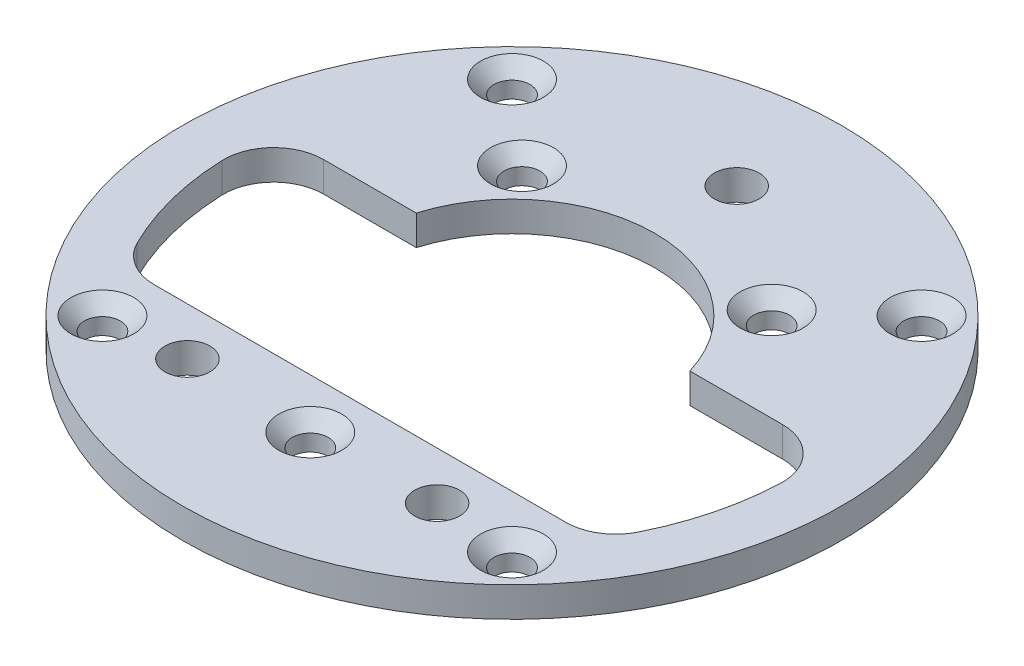
SolidWorks part; units mm, degrees
material "ABS"
ref_plane "Front Plane" through (0, 0, 0) normal (0, 0, 1) x (1, 0, 0)
ref_plane "Top Plane" through (0, 0, 0) normal (0, 1, 0) x (1, 0, 0)
ref_plane "Right Plane" through (0, 0, 0) normal (1, 0, 0) x (0, 0, -1)
sketch "Sketch1" plane through (0, 0, 0) normal (0, 1, 0) x (1, 0, 0)
  circle A0 centre (0, 0) radius 33
  circle A1 centre (0, 0) radius 28
  dimension "D1" = 66
  dimension "D2" = 5
extrude "Boss-Extrude1" add sketch "Sketch1" along normal blind 3
sketch "Sketch2" plane through (0, 3, 0) normal (0, 1, 0) x (1, 0, 0)
  line L0 (-23.5, -15.2233) -> (23.5, -15.2233)
  line L1 (-27.6968, 4.1095) -> (-13.6968, 4.1095)
  line L2 (0, 0) -> (7.7557, 0) construction
  line L3 (13.6968, 4.1095) -> (27.6968, 4.1095)
  line L4 (-20.5061, 20.5061) -> (0, 0) construction
  line L5 (-12.5, 13.5) -> (12.5, 13.5) construction
  circle A0 centre (0, 22.5) radius 2.25 construction
  circle A1 centre (-12.5, -20) radius 2.25 construction
  circle A2 centre (12.5, -20) radius 2.25 construction
  circle A4 centre (-12.5, 13.5) radius 1.5
  circle A6 centre (0, 0) radius 28 construction
  arc A8 (-13.6968, 4.1095) -> (13.6968, 4.1095) centre (0, 0) cw
  arc A9 (27.6968, 4.1095) -> (-27.6968, 4.1095) centre (0, 0) ccw
  arc A10 (23.5, -15.2233) -> (-23.5, -15.2233) centre (0, 0) cw
  circle A11 centre (12.5, 13.5) radius 1.5
  circle A12 centre (0, 0) radius 29 construction
  circle A13 centre (0, 0) radius 33 construction
  circle A14 centre (-20.5061, 20.5061) radius 1.75 construction
  circle A15 centre (20.5061, 20.5061) radius 1.75 construction
  circle A16 centre (20.5061, -20.5061) radius 1.75 construction
  circle A17 centre (-20.5061, -20.5061) radius 1.75 construction
  circle A18 centre (0, -20.2) radius 1.5
  point P15 (0, 13.5)
  point P19 (0, 0)
  point P44 (0, 0)
  circle M2 centre (0, 0) radius 28
  dimension "D5" = 4.5
  dimension "D6" = 4.5
  dimension "D7" = 4.5
  dimension "D12" = 14.3
  dimension "D16" = 3.5
  dimension "D11" = 3
  dimension "D1" = 25
  dimension "D2" = 12.5
  dimension "D3" = 22.5
  dimension "D4" = 20
  dimension "D14" = 4
  dimension "D15" = 135
  dimension "D8" = 14
  dimension "D9" = 14
  dimension "D10" = 47
  dimension "D18" = 25
  dimension "D19" = 20.2
  dimension "D13" = 13.5
  dimension "D17" = 4
extrude "Saliente-Extruir1" add sketch "Sketch2" against normal up to surface (3 mm away) contours L1 A8 L3 M2 | L0 M2 region at (0, 3, 15.7104) region at (0, 3, -15.6634) up to face at (0, 0, 33)
sketch "Croquis1" plane through (0, 3, 0) normal (0, 1, 0) x (1, 0, 0)
  circle A0 centre (-20.5061, 20.5061) radius 1.75 construction
  circle A1 centre (-20.5061, 20.5061) radius 1.75
  circle A2 centre (0, 22.5) radius 2.25 construction
  circle A3 centre (0, 22.5) radius 2.25
  circle A4 centre (20.5061, 20.5061) radius 1.75 construction
  circle A5 centre (20.5061, 20.5061) radius 1.75
  circle A12 centre (12.5, -20) radius 2.25 construction
  circle A13 centre (12.5, -20) radius 2.25
  circle A14 centre (-12.5, -20) radius 2.25 construction
  circle A15 centre (-12.5, -20) radius 2.25
  circle A16 centre (-20.5061, -20.5061) radius 1.75 construction
  circle A17 centre (-20.5061, -20.5061) radius 1.75
  circle A18 centre (20.5061, -20.5061) radius 1.75 construction
  circle A19 centre (20.5061, -20.5061) radius 1.75
extrude "Cortar-Extruir1" cut sketch "Croquis1" against normal up to next
hole_wizard "CSK for M3 Flat Head Machine Screw1" positions "Sketch4" profile "Sketch5" countersink size "M3" standard "ANSI Metric" end condition through all
sketch "Sketch4" plane through (0, 3, 0) normal (0, 1, 0) x (1, 0, 0)
  point P0 (-20.5061, 20.5061)
  point P3 (20.5061, 20.5061)
  point P6 (20.5061, -20.5061)
  point P9 (-20.5061, -20.5061)
sketch "Sketch5" plane through (-20.5061, 3, -20.5061) normal (1, 0, 0) x (0, 0, 1)
  line L0 (0, 0) -> (0, 3)
  line L1 (0, 3) -> (1.8, 3)
  line L2 (1.8, 3) -> (1.8, 1.35)
  line L3 (1.8, 1.35) -> (3.15, 0)
  line L5 (3.15, 0) -> (0, 0)
  line L6 (-1.8, 1.35) -> (-3.15, 0) construction
  line L11 (0, -6.35) -> (0, 107.95) construction
  dimension "Thru Hole Dia." = 3.6
  dimension "Thru Hole Depth" = 3
  dimension "Near C'Sink Dia." = 6.3
  dimension "Near C'Sink Angle" = 90
hole_wizard "CSK for M3 Flat Head Machine Screw2" positions "Sketch6" profile "Sketch7" countersink size "M3" standard "ANSI Metric" end condition through all
sketch "Sketch6" plane through (0, 3, 0) normal (0, 1, 0) x (1, 0, 0)
  point P12 (-12.5, 13.5)
  point P15 (12.5, 13.5)
  point P18 (0, -20.2)
sketch "Sketch7" plane through (-12.5, 3, -13.5) normal (1, 0, 0) x (0, 0, 1)
  line L0 (0, 0) -> (0, 3)
  line L1 (0, 3) -> (1.8, 3)
  line L2 (1.8, 3) -> (1.8, 1.35)
  line L3 (1.8, 1.35) -> (3.15, 0)
  line L5 (3.15, 0) -> (0, 0)
  line L6 (-1.8, 1.35) -> (-3.15, 0) construction
  line L11 (0, -6.35) -> (0, 107.95) construction
  dimension "Thru Hole Dia." = 3.6
  dimension "Thru Hole Depth" = 3
  dimension "Near C'Sink Dia." = 6.3
  dimension "Near C'Sink Angle" = 90
fillet "Fillet1" radius 5 4 edges at (-27.6968, 1.5, -4.1095) (27.6968, 1.5, -4.1095) (23.5, 1.5, 15.2233) (-23.5, 1.5, 15.2233)
equation "\"D2@Sketch2\"=\"D1@Sketch2\"/2"
equation "\"D6@Sketch2\"=\"D5@Sketch2\""
equation "\"D7@Sketch2\"=\"D6@Sketch2\""
